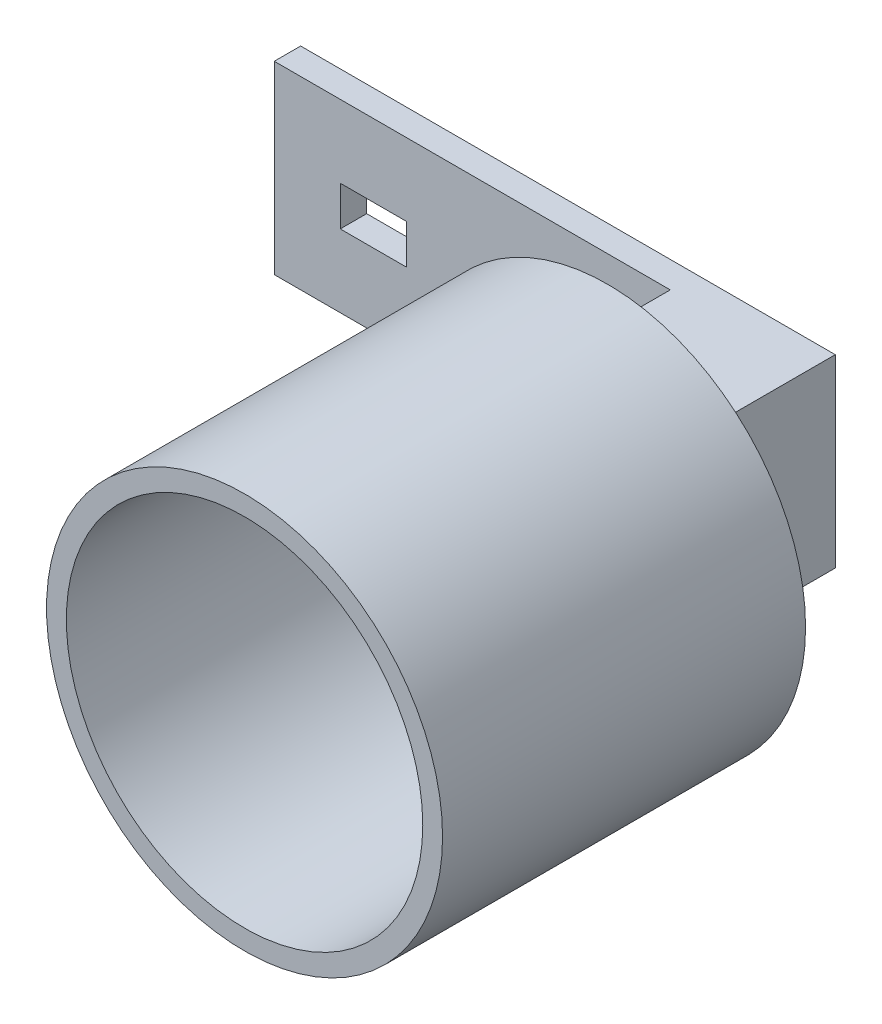
SolidWorks part; units mm, degrees
ref_plane "Plan de face" through (0, 0, 0) normal (0, 0, 1) x (1, 0, 0)
ref_plane "Plan de dessus" through (0, 0, 0) normal (0, 1, 0) x (1, 0, 0)
ref_plane "Plan de droite" through (0, 0, 0) normal (1, 0, 0) x (0, 0, -1)
sketch "Esquisse1" plane through (0, 0, 0) normal (0, 0, 1) x (1, 0, 0)
  circle A0 centre (0, 0) radius 30
  dimension "D1" = 60
extrude "Boss.-Extru.1" add sketch "Esquisse1" along normal blind 55 contours A0
sketch "Esquisse2" plane through (0, 0, 55) normal (0, 0, 1) x (1, 0, 0)
  circle A0 centre (0, 0) radius 27
  circle A1 centre (0, 0) radius 30 construction
  dimension "D1" = 3
extrude "Enlèv. mat.-Extru.1" cut sketch "Esquisse2" against normal blind 47 contours A0
sketch "Esquisse3" plane through (0, 0, 0) normal (0, 0, -1) x (-1, 0, 0)
  line L1 (-10.5, -14) -> (10.5, -14)
  line L2 (-10.5, -14) -> (-10.5, 14)
  line L3 (-10.5, 14) -> (10.5, 14)
  line L4 (10.5, -14) -> (10.5, 14)
  line L5 (-10.5, -14) -> (10.5, 14) construction
  line L6 (-10.5, 14) -> (10.5, -14) construction
  point P0 (0, 0)
  dimension "D1" = 28
  dimension "D2" = 21
extrude "Boss.-Extru.2" add sketch "Esquisse3" along normal blind 24
sketch "Esquisse4" plane through (-10.5, 0, 0) normal (-1, 0, 0) x (0, 0, 1)
  line L0 (0, -14) -> (0, 14) construction
  line L1 (-24, 14) -> (-20, 14)
  line L2 (-24, 14) -> (-24, -14)
  line L3 (-24, -14) -> (-20, -14)
  line L4 (-20, 14) -> (-20, -14)
  line L5 (-24, 14) -> (-20, -14) construction
  line L6 (-24, -14) -> (-20, 14) construction
  line L7 (-24, 14) -> (0, 14) construction
  line L8 (-24, -14) -> (0, -14) construction
  point P0 (-22, 0)
  dimension "D1" = 20
  dimension "D2" = 4
  dimension "D3" = 0
  dimension "D4" = 0
extrude "Boss.-Extru.3" add sketch "Esquisse4" along normal blind 60
sketch "Esquisse5" plane through (0, 0, -24) normal (0, 0, -1) x (-1, 0, 0)
  line L0 (-10.5, -14) -> (70.5, -14) construction
  line L1 (50.5, -3) -> (60.5, -3)
  line L2 (50.5, -3) -> (50.5, 3)
  line L3 (50.5, 3) -> (60.5, 3)
  line L4 (60.5, -3) -> (60.5, 3)
  line L5 (50.5, -3) -> (60.5, 3) construction
  line L6 (50.5, 3) -> (60.5, -3) construction
  line L8 (70.5, 14) -> (70.5, -14) construction
  point P0 (55.5, 0)
  dimension "D1" = 6
  dimension "D2" = 10
  dimension "D3" = 11
  dimension "D4" = 10
extrude "Enlèv. mat.-Extru.2" cut sketch "Esquisse5" against normal up to next
equation "\"taille\"= 3mm"
